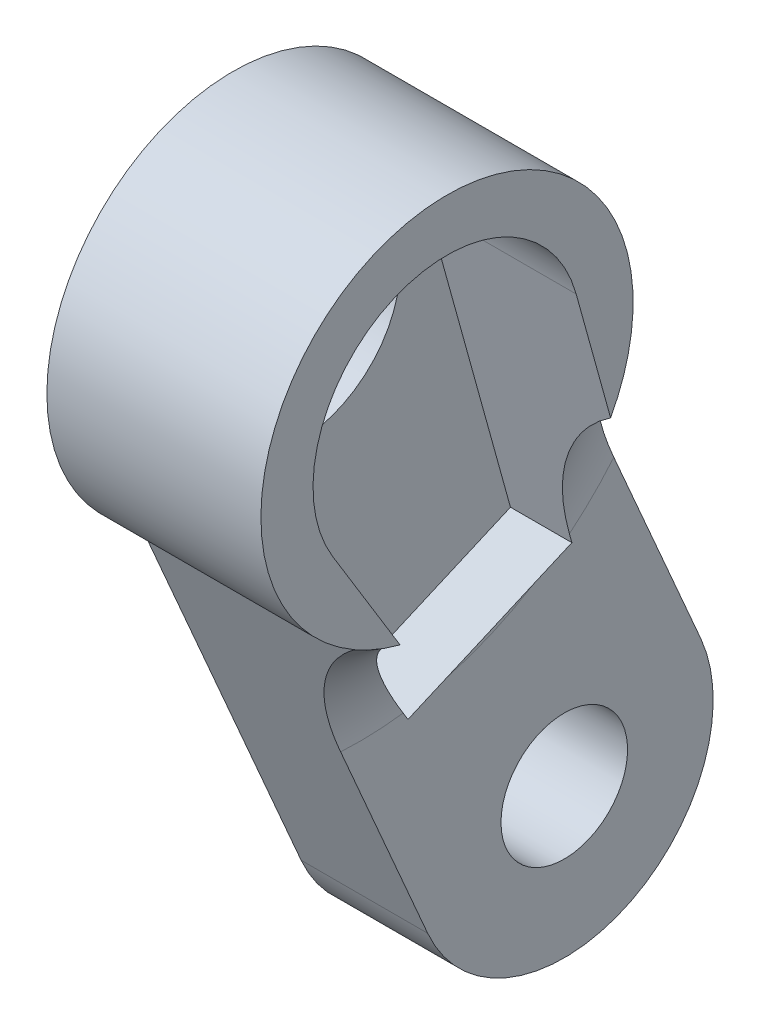
SolidWorks part; units mm, degrees
ref_plane "Front Plane" through (0, 0, 0) normal (0, 0, 1) x (1, 0, 0)
ref_plane "Top Plane" through (0, 0, 0) normal (0, 1, 0) x (1, 0, 0)
ref_plane "Right Plane" through (0, 0, 0) normal (1, 0, 0) x (0, 0, -1)
ref_plane "Plane1" through (-31.5964, 0, 0) normal (1, 0, 0) x (0, 0, -1)
sketch "Sketch1" plane through (-31.5964, 0, 0) normal (1, 0, 0) x (0, 0, -1)
  line L0 (32.0245, -57.085) -> (36.3305, -67.0097)
  line L1 (43.6695, -63.8256) -> (39.3636, -53.9009)
  arc A1 (36.3305, -67.0097) -> (43.6695, -63.8256) centre (40, -65.4176) ccw
  arc A2 (39.3636, -53.9009) -> (32.0245, -57.085) centre (34.5, -52.7408) ccw
  dimension "D2" = 4
  dimension "D3" = 5
  dimension "D1" = 13.8186
extrude "Boss-Extrude1" add sketch "Sketch1" against normal blind 5.75
sketch "Sketch2" plane through (-31.5964, 0, 0) normal (1, 0, 0) x (0, 0, -1)
  line L0 (32.0245, -57.085) -> (36.3305, -67.0097)
  line L1 (43.6695, -63.8256) -> (39.3636, -53.9009)
  line L2 (43.6695, -63.8256) -> (39.3636, -53.9009) construction
  arc A0 (39.3636, -53.9009) -> (32.0245, -57.085) centre (34.5, -52.7408) cw
  arc A1 (36.3305, -67.0097) -> (43.6695, -63.8256) centre (40, -65.4176) ccw
  arc A3 (39.3636, -53.9009) -> (32.0245, -57.085) centre (34.5, -52.7408) ccw construction
extrude "Cut-Extrude1" cut sketch "Sketch2" against normal blind 2.35
draft "Draft1" [suppressed] type of draft neutral plane draft angle 45 faces to draft 1 parameters "D1"=45
hole_wizard "Hole1" positions "Sketch4" profile "Sketch3" legacy end condition through all
sketch "Sketch4" plane through (-37.3464, 0, 0) normal (-1, 0, 0) x (0, 0, 1)
  point P0 (-40, -65.4176)
sketch "Sketch3" plane through (-37.3464, -65.4176, -40) normal (0, 1, 0) x (0, 0, 1)
  line L0 (0, 0) -> (0, 5.75)
  line L1 (0, 5.75) -> (1.7, 5.75)
  line L2 (1.7, 5.75) -> (1.7, 0)
  line L3 (1.7, 0) -> (0, 0)
  line L4 (0, 110) -> (0, -10) construction
  dimension "Diameter" = 3.4
  dimension "Depth" = 5.75
hole_wizard "Hole2" positions "Sketch6" profile "Sketch5" legacy end condition through all
sketch "Sketch6" plane through (-31.5964, 0, 0) normal (1, 0, 0) x (0, 0, -1)
  point P0 (34.5, -52.7408)
sketch "Sketch5" plane through (-31.5964, -52.7408, -34.5) normal (0, 1, 0) x (0, 0, -1)
  line L0 (0, 0) -> (0, 5.75)
  line L1 (0, 5.75) -> (2.75, 5.75)
  line L2 (2.75, 5.75) -> (2.75, 2.8)
  line L3 (2.75, 2.8) -> (2.2, 2.8)
  line L4 (2.2, 2.8) -> (2.2, 0)
  line L5 (2.2, 0) -> (0, 0)
  line L6 (0, 110) -> (0, -10) construction
  dimension "Diameter" = 5.5
  dimension "Depth" = 5.75
  dimension "C-Bore Diameter" = 4.4
  dimension "C-Bore Depth" = 2.8
chamfer "Chamfer1" [suppressed] distance 0.5 angle 45
fillet "Fillet1" radius 4.4 1 edges at (-33.9464, -57.3277, -36.4901) tangent propagation no
sketch "Sketch7" plane through (-31.5964, 0, 0) normal (1, 0, 0) x (0, 0, -1)
  line L0 (34.5, -52.7408) -> (40, -65.4176) construction
  line L1 (37.9697, -51.7809) -> (40.2042, -59.8585)
  line L2 (40.2042, -59.8585) -> (35.8008, -61.769)
  line L3 (35.8008, -61.769) -> (31.4287, -54.6188)
  arc A0 (37.9697, -51.7809) -> (31.4287, -54.6188) centre (34.5, -52.7408) ccw
  point P7 (38.0025, -60.8137)
  dimension "D1" = 7.2
  dimension "D2" = 4.8
  dimension "D3" = 8.8
extrude "Cut-Extrude2" cut sketch "Sketch7" against normal blind 4
